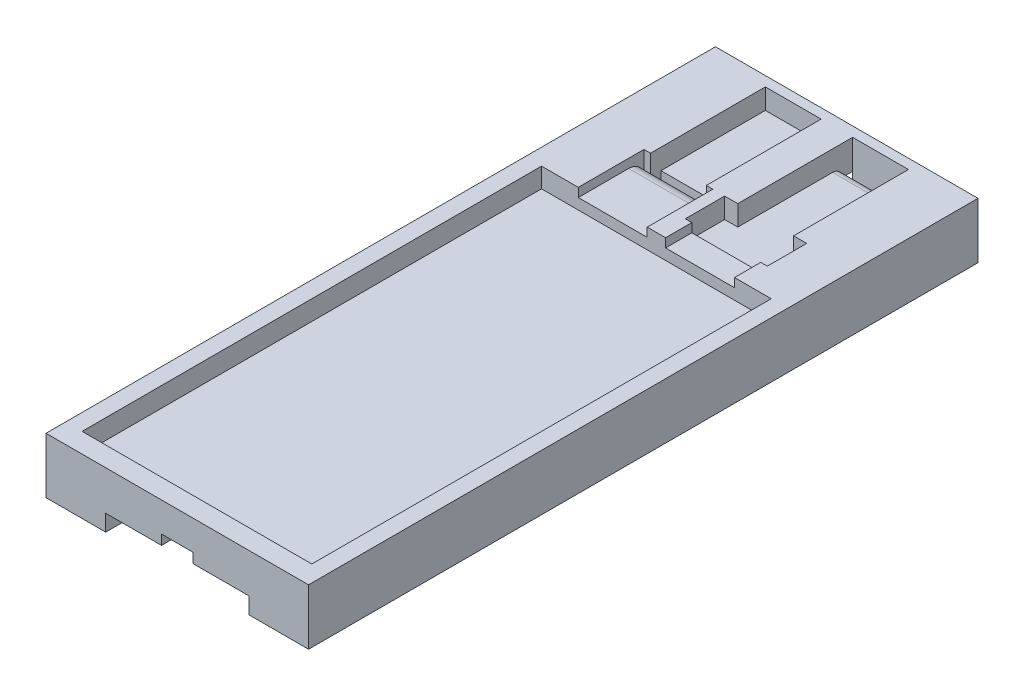
SolidWorks part; units mm, degrees
ref_plane "Front Plane" through (0, 0, 0) normal (0, 0, 1) x (1, 0, 0)
ref_plane "Top Plane" through (0, 0, 0) normal (0, 1, 0) x (1, 0, 0)
ref_plane "Right Plane" through (0, 0, 0) normal (1, 0, 0) x (0, 0, -1)
sketch "Sketch1" plane through (0, 0, 0) normal (0, 1, 0) x (1, 0, 0)
  line L1 (-20, -40) -> (20, -40)
  line L2 (-20, -40) -> (-20, 62)
  line L3 (-20, 62) -> (20, 62)
  line L4 (20, -40) -> (20, 62)
  dimension "D1" = 40
  dimension "D2" = 102
  dimension "D3" = 40
  dimension "D4" = 20
extrude "Boss-Extrude1" add sketch "Sketch1" along normal blind 8.5
sketch "Sketch2" plane through (0, 8.5, 0) normal (0, 1, 0) x (1, 0, 0)
  line L0 (-20, -40) -> (20, -40) construction
  line L1 (-17.5, -37) -> (17.5, -37)
  line L2 (-17.5, -37) -> (-17.5, 33)
  line L3 (-17.5, 33) -> (17.5, 33)
  line L4 (17.5, -37) -> (17.5, 33)
  line L5 (20, -40) -> (20, 62) construction
  line L6 (-20, 62) -> (-20, -40) construction
  dimension "D1" = 3
  dimension "D2" = 35
  dimension "D3" = 2.5
  dimension "D4" = 2.5
  dimension "D5" = 70
extrude "Cut-Extrude1" cut sketch "Sketch2" against normal blind 3
sketch "Sketch3" plane through (0, 8.5, 0) normal (0, 1, 0) x (1, 0, 0)
  line L0 (17.5, 33) -> (-17.5, 33) construction
  line L1 (-11.9, 33) -> (-1.4, 33)
  line L2 (-11.9, 33) -> (-11.9, 43)
  line L3 (-11.9, 43) -> (-1.4, 43)
  line L4 (-1.4, 33) -> (-1.4, 43)
  line L5 (0, 0) -> (0, 15.5865) construction
  line L6 (1.4, 33) -> (1.4, 43)
  line L7 (11.9, 43) -> (1.4, 43)
  line L8 (11.9, 33) -> (11.9, 43)
  line L9 (11.9, 33) -> (1.4, 33)
  dimension "D1" = 10
  dimension "D2" = 10.5
  dimension "D3" = 1.4
extrude "Cut-Extrude2" cut sketch "Sketch3" against normal blind 1.35
sketch "Sketch4" plane through (0, 8.5, 0) normal (0, 1, 0) x (1, 0, 0)
  line L0 (11.9, 43) -> (1.4, 43) construction
  line L1 (0.4, 37) -> (12.9, 37)
  line L2 (0.4, 37) -> (0.4, 43)
  line L3 (0.4, 43) -> (12.9, 43)
  line L4 (12.9, 37) -> (12.9, 43)
  line L5 (1.4, 43) -> (1.4, 33) construction
  dimension "D1" = 6
  dimension "D2" = 12.5
  dimension "D3" = 1
extrude "Cut-Extrude3" cut sketch "Sketch4" against normal blind 3.1
sketch "Sketch5" plane through (0, 8.5, 0) normal (0, 1, 0) x (1, 0, 0)
  line L0 (12.9, 43) -> (0.4, 43) construction
  line L1 (2.4, 43) -> (10.9, 43)
  line L2 (2.4, 43) -> (2.4, 60.5)
  line L3 (2.4, 60.5) -> (10.9, 60.5)
  line L4 (10.9, 43) -> (10.9, 60.5)
  line L5 (12.9, 37) -> (12.9, 43) construction
  dimension "D1" = 17.5
  dimension "D2" = 8.5
  dimension "D3" = 2
extrude "PCB place" cut sketch "Sketch5" against normal up to surface (3.1 mm away) up to face at (6.65, 5.4, -40)
sketch "Sketch6" plane through (0, 5.4, 0) normal (0, 1, 0) x (1, 0, 0)
  line L0 (10.9, 43) -> (10.9, 60.5) construction
  line L1 (2.4, 60.5) -> (10.9, 60.5)
  line L2 (2.4, 60.5) -> (2.4, 58.9)
  line L3 (2.4, 58.9) -> (10.9, 58.9)
  line L4 (10.9, 60.5) -> (10.9, 58.9)
  dimension "D1" = 1.6
extrude "Nickel strip hole" cut sketch "Sketch6" against normal through all
sketch "Sketch7" plane through (0, 8.5, 0) normal (0, 1, 0) x (1, 0, 0)
  line L0 (10.9, 60.5) -> (2.4, 60.5) construction
  line L1 (-2.4, 43) -> (-10.9, 43)
  line L2 (-2.4, 43) -> (-2.4, 60.5)
  line L3 (-2.4, 60.5) -> (-10.9, 60.5)
  line L4 (-10.9, 43) -> (-10.9, 60.5)
  line L5 (-11.9, 43) -> (-11.9, 33) construction
  line L6 (-1.4, 43) -> (-11.9, 43) construction
  dimension "D1" = 8.5
  dimension "D2" = 1
extrude "Cut-Extrude4" cut sketch "Sketch7" against normal up to surface (3.1 mm away) up to face at (6.65, 5.4, -45.475)
sketch "Sketch8" plane through (0, 5.4, 0) normal (0, 1, 0) x (1, 0, 0)
  line L0 (-10.9, 60.5) -> (-10.9, 43) construction
  line L1 (-2.4, 43) -> (-10.9, 43)
  line L2 (-2.4, 43) -> (-2.4, 44.6)
  line L3 (-2.4, 44.6) -> (-10.9, 44.6)
  line L4 (-10.9, 43) -> (-10.9, 44.6)
  dimension "D1" = 1.6
extrude "Cut-Extrude5" cut sketch "Sketch8" against normal blind 10
sketch "Sketch9" plane through (0, 0, 0) normal (0, -1, 0) x (1, 0, 0)
  line L0 (20, -62) -> (-20, -62) construction
  line L1 (-2.4, -62) -> (-10.9, -62)
  line L2 (-2.4, -62) -> (-2.4, 40)
  line L3 (-2.4, 40) -> (-10.9, 40)
  line L4 (-10.9, -62) -> (-10.9, 40)
  line L5 (2.4, -62) -> (10.9, -62)
  line L6 (2.4, -62) -> (2.4, 40)
  line L7 (2.4, 40) -> (10.9, 40)
  line L8 (10.9, -62) -> (10.9, 40)
  line L9 (-10.9, -43) -> (-10.9, -44.6) construction
  line L10 (-2.4, -44.6) -> (-2.4, -43) construction
  line L11 (-20, 40) -> (20, 40) construction
  line L12 (2.4, -60.5) -> (2.4, -58.9) construction
  line L13 (10.9, -58.9) -> (10.9, -60.5) construction
extrude "Nickel strip rail" cut sketch "Sketch9" against normal blind 2.5
fillet "Fillet3" 2 edges at (-6.65, 7.15, -43) (-6.65, 2.5, -43) type full round first side face at (-6.65, 7.15, -39.6667) second side face at (-6.65, 2.5, -1.5) middle face at (-6.65, 4.825, -43)
fillet "Fillet4" 2 edges at (6.65, 5.4, -58.9) (6.65, 2.5, -58.9) type full round first side face at (6.65, 5.4, -45.475) second side face at (6.65, 2.5, -9.45) middle face at (6.65, 3.95, -58.9)
sketch "Sketch10" plane through (0, 0, 40) normal (0, 0, 1) x (1, 0, 0)
  line L0 (2.4, 2.5) -> (2.4, 0) construction
  line L1 (-2.4, 0) -> (2.4, 0)
  line L2 (-2.4, 0) -> (-2.4, 4)
  line L3 (-2.4, 4) -> (2.4, 4)
  line L4 (2.4, 0) -> (2.4, 4)
  line L5 (-2.4, 0) -> (2.4, 4) construction
  line L6 (-2.4, 4) -> (2.4, 0) construction
  point P4 (0, 2)
  dimension "D1" = 4
extrude "Cut-Extrude6" cut sketch "Sketch10" against normal up to surface (102 mm away) up to face at (0, 2.25, -62)
